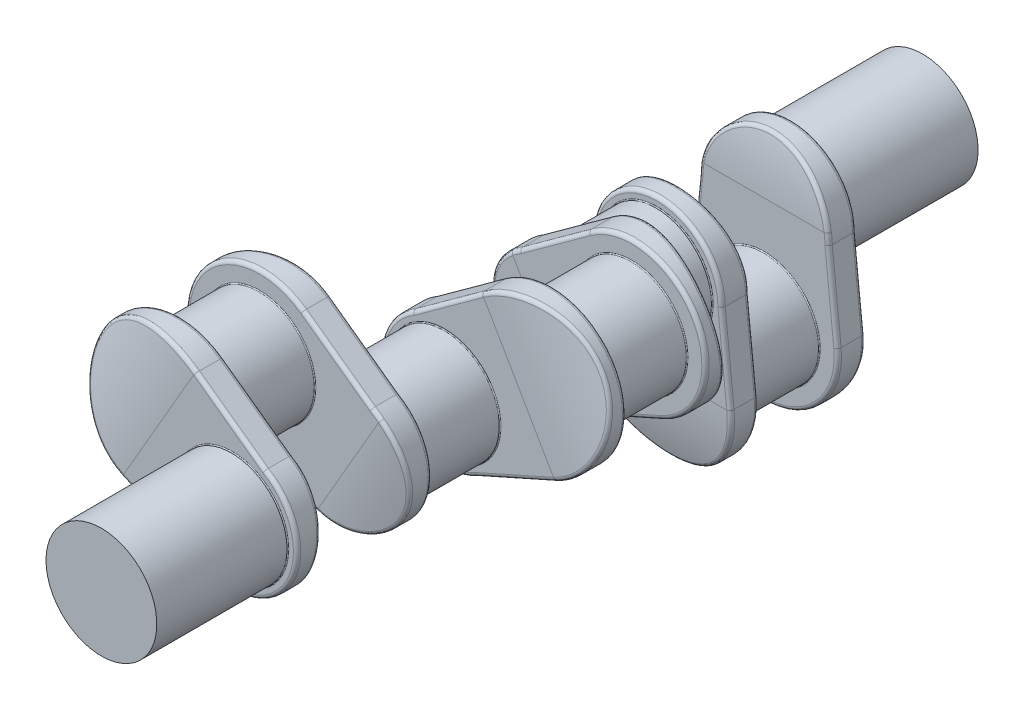
SolidWorks part; units mm, degrees
ref_plane "Front Plane" through (0, 0, 0) normal (0, 0, 1) x (1, 0, 0)
ref_plane "Top Plane" through (0, 0, 0) normal (0, 1, 0) x (1, 0, 0)
ref_plane "Right Plane" through (0, 0, 0) normal (1, 0, 0) x (0, 0, -1)
sketch "Sketch2" plane through (0, 0, 0) normal (0, 0, 1) x (1, 0, 0)
  circle A0 centre (0, 0) radius 38.1
  dimension "D1" = 76.2
extrude "Boss-Extrude1" add sketch "Sketch2" along normal blind 27.31
sketch "Sketch3" plane through (0, 0, 27.31) normal (0, 0, 1) x (1, 0, 0)
  line L0 (-44.45, 63.5) -> (-50.5257, 5.272)
  line L1 (44.45, 63.5) -> (50.5257, 5.272)
  arc A0 (-50.5257, 5.272) -> (50.5257, 5.272) centre (0, 0) ccw
  arc A1 (44.45, 63.5) -> (-44.45, 63.5) centre (0, 63.5) ccw
  circle A2 centre (0, 0) radius 38.1 construction
  dimension "D1" = 12.7
  dimension "D3" = 88.9
  dimension "D2" = 63.5
extrude "Boss-Extrude2" add sketch "Sketch3" along normal blind 19
sketch "Sketch4" plane through (0, 0, 46.31) normal (0, 0, 1) x (1, 0, 0)
  circle A0 centre (0, 63.5) radius 38.1
  dimension "D1" = 76.2
extrude "Boss-Extrude3" add sketch "Sketch4" along normal blind 26.67
sketch "Sketch5" plane through (0, 0, 0) normal (1, 0, 0) x (0, 0, -1)
  line L0 (-46.31, -50.8) -> (-27.31, -50.8) construction
  line L1 (-46.31, 5.272) -> (-63.8712, 5.272)
  line L2 (-63.8712, 5.272) -> (-63.8712, -50.8)
  line L3 (-63.8712, -50.8) -> (-36.81, -50.8)
  arc A0 (-46.31, 5.272) -> (-36.81, -50.8) centre (122.6899, 5.064) ccw
  dimension "D1" = 169
extrude "Cut-Extrude1" cut sketch "Sketch5" against normal mid plane 179.67
sketch "Sketch6" plane through (0, 0, 0) normal (1, 0, 0) x (0, 0, -1)
  line L0 (-27.31, 107.95) -> (-46.31, 107.95) construction
  line L1 (-32.31, 107.95) -> (-18.2918, 107.95)
  line L2 (-18.2918, 107.95) -> (-18.2918, 63.5)
  line L3 (-18.2918, 63.5) -> (-27.31, 63.5)
  arc A0 (-32.31, 107.95) -> (-27.31, 63.5) centre (-196.2738, 67.0002) cw
  dimension "D1" = 169
  dimension "D2" = 5
extrude "Cut-Extrude2" cut sketch "Sketch6" against normal mid plane 179.67
fillet "Fillet1" radius 2.54 10 edges at (-47.4878, 34.386, 27.31) (0, -50.8, 27.31) (-47.4878, 34.386, 46.31) (-50.547, 5.0641, 46.31) (0.0331, -50.8, 36.81) (50.547, 5.0641, 46.31) (3.1078, 107.8412, 32.2829) (47.4878, 34.386, 27.31) (0, 107.95, 46.31) (47.4878, 34.386, 46.31)
fillet "Fillet2" radius 0.64 2 edges at (38.1, 63.5, 46.31) (38.1, 0, 27.31)
mirror "Mirror1" about plane through (0, 0, 0) normal (0, 0, 1) of bodies 105
ref_axis "Axis1" through (0, 63.5, -479.2375) along (0, 0, 1)
pattern_linear "LPattern1" count 3 spacing 145.96 along (0, 0, 1) of bodies 106
move or copy body "Body-Move/Copy1" bodies to move or copy 107 copy no rotation origin (0, 63.5, 0) rotation axis (0, 0, 1) rotation angle 120
move or copy body "Body-Move/Copy2" bodies to move or copy 108 copy no rotation origin (0, 63.5, 0) rotation axis (0, 0, -1) rotation angle 120
sketch "Sketch7" plane through (0, 0, -72.98) normal (0, 0, -1) x (-1, 0, 0)
  circle A0 centre (0, 63.5) radius 38.1 construction
  circle A1 centre (0, 63.5) radius 38.1
extrude "Boss-Extrude4" add sketch "Sketch7" along normal blind 63.5
sketch "Sketch8" plane through (0, 0, 364.9) normal (0, 0, 1) x (1, 0, 0)
  circle A0 centre (0, 63.5) radius 38.1 construction
  circle A1 centre (0, 63.5) radius 38.1
extrude "Boss-Extrude5" add sketch "Sketch8" along normal blind 63.5
combine bodies "Combine1" operation type add bodies to combine 111 109 112
